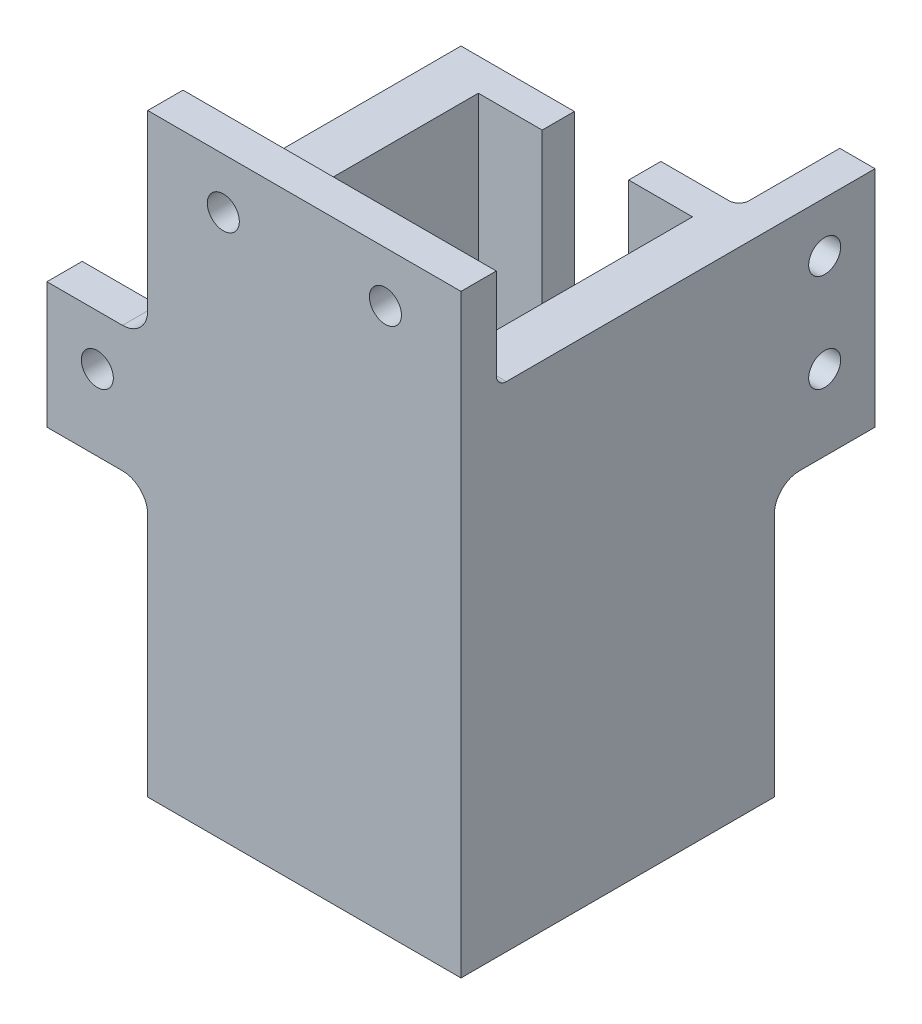
SolidWorks part; units mm, degrees
ref_plane "Front" through (0, 0, 0) normal (0, 0, 1) x (1, 0, 0)
ref_plane "Top" through (0, 0, 0) normal (0, 1, 0) x (1, 0, 0)
ref_plane "Right" through (0, 0, 0) normal (1, 0, 0) x (0, 0, -1)
sketch "Sketch1" plane through (0, 0, 0) normal (0, 1, 0) x (1, 0, 0)
  line L0 (8.583, 21.25) -> (8.583, 27.64)
  line L1 (-21.25, 21.25) -> (-8.583, 21.25)
  line L2 (-21.25, 21.25) -> (-21.25, -21.25)
  line L3 (-21.25, -21.25) -> (21.25, -21.25)
  line L4 (21.25, 21.25) -> (21.25, -21.25)
  line L5 (-21.25, 21.25) -> (21.25, -21.25) construction
  line L6 (-21.25, -21.25) -> (21.25, 21.25) construction
  line L7 (-31.083, 27.64) -> (-8.583, 27.64)
  line L8 (-31.083, 27.64) -> (-31.083, -34.526)
  line L9 (-31.083, -34.526) -> (31.083, -34.526)
  line L10 (31.083, 27.64) -> (31.083, -34.526)
  line L13 (-8.583, 21.25) -> (-8.583, 27.64)
  line L14 (8.583, 27.64) -> (31.083, 27.64)
  line L15 (8.583, 21.25) -> (21.25, 21.25)
  point P0 (0, 0)
  point P6 (0, 0)
  point P15 (0, -34.526)
  dimension "D1" = 42.5
  dimension "D3" = 22.5
  dimension "D4" = 22.5
  dimension "D6" = 6.39
  dimension "D7" = 62.166
extrude "Boss-Extrude1" add sketch "Sketch1" along normal blind 48
sketch "Sketch2" plane through (0, 0, 0) normal (0, 1, 0) x (1, 0, 0)
  line L0 (-31.083, 27.64) -> (-31.083, -34.526) construction
  line L1 (-31.083, 27.64) -> (31.083, 27.64)
  line L2 (-31.083, 27.64) -> (-31.083, -34.526)
  line L3 (-31.083, -34.526) -> (31.083, -34.526)
  line L4 (31.083, 27.64) -> (31.083, -34.526)
  line L5 (31.083, -34.526) -> (31.083, 27.64) construction
  line L6 (-31.083, -34.526) -> (31.083, -34.526) construction
  line L7 (31.083, 27.64) -> (8.583, 27.64) construction
  point P0 (0, 0)
extrude "Boss-Extrude2" add sketch "Sketch2" against normal blind 50
sketch "Sketch5" plane through (0, 0, -27.64) normal (0, 0, -1) x (-1, 0, 0)
  line L0 (-31.083, 48) -> (-24.083, 48)
  line L1 (-31.083, 48) -> (-8.583, 48) construction
  line L2 (-31.083, 48) -> (-31.083, -50) construction
  line L3 (-24.083, 48) -> (-24.083, 3.575)
  line L4 (-24.083, 3.575) -> (-31.083, 3.575)
  line L5 (-31.083, 3.575) -> (-31.083, 48)
  dimension "D1" = 44.425
  dimension "D2" = 7
extrude "Boss-Extrude3" add sketch "Sketch5" along normal blind 20
sketch "Sketch8" plane through (0, 48, 0) normal (0, 1, 0) x (1, 0, 0)
  line L0 (31.083, -27.526) -> (-31.083, -27.526)
  line L1 (31.083, -34.526) -> (31.083, 47.64) construction
  line L2 (-31.083, 27.64) -> (-31.083, -34.526) construction
  line L3 (-31.083, -27.526) -> (-31.083, -34.526)
  line L4 (-31.083, -34.526) -> (31.083, -34.526)
  line L5 (-31.083, -34.526) -> (31.083, -34.526) construction
  line L6 (31.083, -34.526) -> (31.083, -27.526)
  dimension "D1" = 7
extrude "Boss-Extrude4" add sketch "Sketch8" along normal blind 20
sketch "Sketch10" plane through (-31.083, 0, 0) normal (-1, 0, 0) x (0, 0, 1)
  line L0 (34.526, 3.575) -> (34.526, 28.575)
  line L1 (34.526, 68) -> (34.526, -50) construction
  line L2 (34.526, 28.575) -> (27.526, 28.575)
  line L3 (27.526, 28.575) -> (27.526, 3.575)
  line L4 (27.526, 3.575) -> (34.526, 3.575)
  line L6 (-27.64, -50) -> (34.526, -50) construction
  point P4 (34.776, 3.575)
  point P7 (34.776, 3.575)
  dimension "D1" = 7
  dimension "D2" = 25
  dimension "D3" = 53.575
extrude "Boss-Extrude5" add sketch "Sketch10" along normal blind 20
sketch "Sketch7" plane through (24.083, 0, 0) normal (-1, 0, 0) x (0, 0, 1)
  line L0 (-47.64, 48) -> (-27.64, 48) construction
  line L1 (-47.64, 3.575) -> (-27.64, 3.575) construction
  circle A0 centre (-37.64, 38) radius 3.175
  circle A1 centre (-37.64, 18.575) radius 3.175
  point P7 (-37.64, 48)
  dimension "D1" = 6.35
  dimension "D2" = 10
  dimension "D3" = 15
extrude "Cut-Extrude1" cut sketch "Sketch7" against normal through all
sketch "Sketch9" plane through (0, 0, 27.526) normal (0, 0, -1) x (-1, 0, 0)
  line L1 (-31.083, 68) -> (-31.083, 48) construction
  line L2 (31.083, 68) -> (31.083, 48) construction
  circle A0 centre (-16.083, 58) radius 3.175
  circle A1 centre (16.083, 58) radius 3.175
  point P8 (0, 0)
  point P9 (-31.083, 58)
  dimension "D1" = 6.35
  dimension "D2" = 15
  dimension "D3" = 15
extrude "Cut-Extrude2" cut sketch "Sketch9" against normal through all
sketch "Sketch11" plane through (0, 0, 27.526) normal (0, 0, -1) x (-1, 0, 0)
  line L0 (51.083, 3.575) -> (31.083, 3.575) construction
  line L1 (51.083, 28.575) -> (31.083, 28.575) construction
  circle A0 centre (41.083, 18.575) radius 3.175
  point P4 (0, 0)
  point P7 (41.083, 28.575)
  dimension "D1" = 6.35
  dimension "D2" = 15
extrude "Cut-Extrude3" cut sketch "Sketch11" against normal through all
fillet "Fillet1" radius 2 3 edges at (0, 48, 27.526) (-31.083, 16.075, 27.526) (24.083, 25.7875, -27.64)
fillet "Fillet2" radius 5 3 edges at (-31.083, 28.575, 30.026) (-31.083, 3.575, 30.026) (26.583, 3.575, -27.64)
